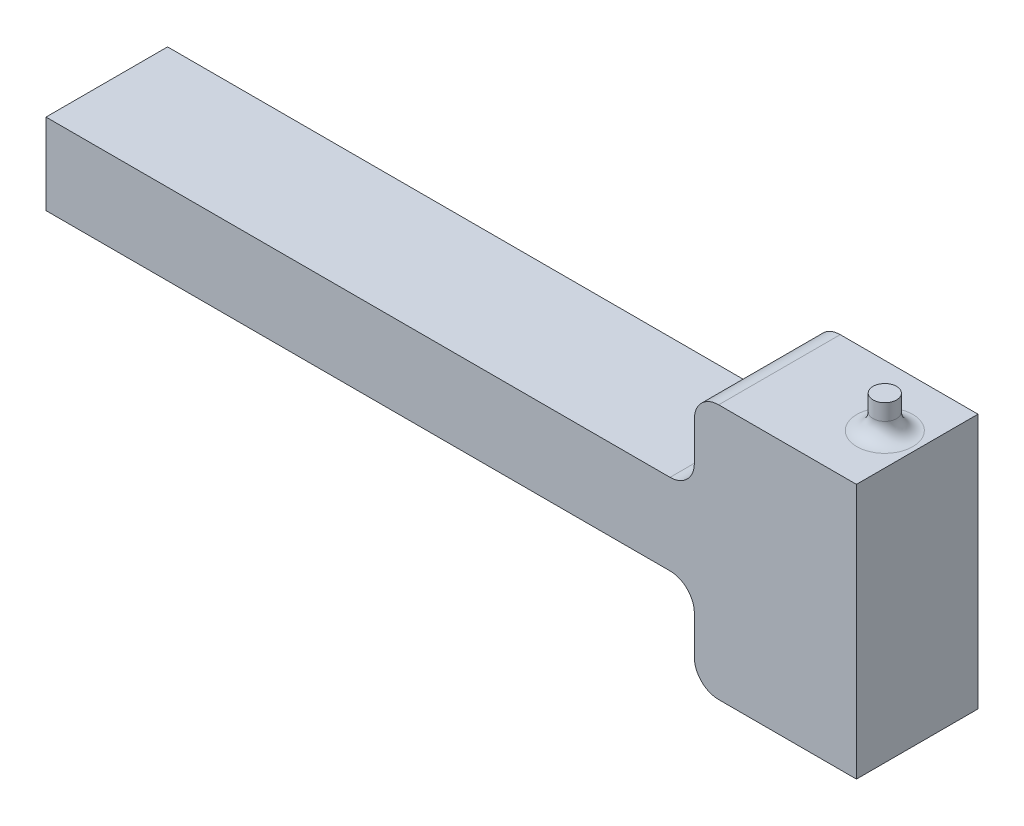
SolidWorks part; units mm, degrees
ref_plane "Front Plane" through (0, 0, 0) normal (0, 0, 1) x (1, 0, 0)
ref_plane "Top Plane" through (0, 0, 0) normal (0, 1, 0) x (1, 0, 0)
ref_plane "Right Plane" through (0, 0, 0) normal (1, 0, 0) x (0, 0, -1)
sketch "Sketch2" plane through (0, 0, 0) normal (0, 1, 0) x (1, 0, 0)
  line L1 (-50, -7.5) -> (50, -7.5)
  line L2 (-50, -7.5) -> (-50, 7.5)
  line L3 (-50, 7.5) -> (50, 7.5)
  line L4 (50, -7.5) -> (50, 7.5)
  line L5 (-50, -7.5) -> (50, 7.5) construction
  line L6 (-50, 7.5) -> (50, -7.5) construction
  point P0 (0, 0)
  dimension "D1" = 100
  dimension "D2" = 15
extrude "Boss-Extrude2" add sketch "Sketch2" along normal mid plane 31.5
sketch "Sketch6" plane through (0, 0, 7.5) normal (0, 0, 1) x (1, 0, 0)
  line L0 (55, 0) -> (-55, 0) construction
  line L1 (-50, 15.75) -> (30, 15.75)
  line L2 (-50, 15.75) -> (-50, 5)
  line L3 (-50, 5) -> (30, 5)
  line L4 (30, 15.75) -> (30, 5)
  line L5 (0, 0) -> (50000, 0) construction
  line L6 (30, -15.75) -> (30, -5)
  line L7 (-50, -15.75) -> (-50, -5)
  line L8 (-50, -15.75) -> (30, -15.75)
  line L9 (-50, -5) -> (30, -5)
  dimension "D1" = 5
  dimension "D2" = 80
extrude "Cut-Extrude3" cut sketch "Sketch6" against normal through all both and the other way through all
fillet "Fillet2" radius 3 4 edges at (30, 15.75, 0) (30, 5, 0) (30, -5, 0) (30, -15.75, 0)
sketch "Sketch7" plane through (0, 15.75, 0) normal (0, 1, 0) x (1, 0, 0)
  line L0 (-55, 0) -> (55, 0) construction
  line L1 (50, -7.5) -> (50, 7.5) construction
  circle A0 centre (46, 0) radius 1.45
  dimension "D1" = 2.9
  dimension "D2" = 4
extrude "Boss-Extrude3" add sketch "Sketch7" along normal blind 4
fillet "Fillet3" radius 2 1 edges at (46, 15.75, -1.45)
